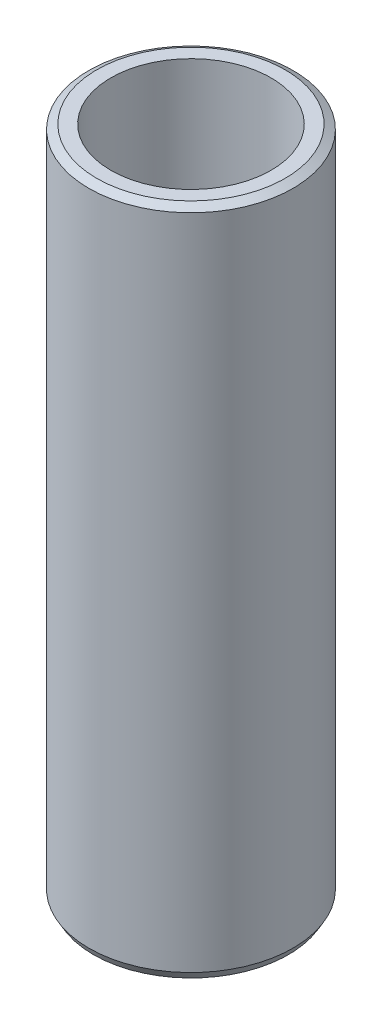
SolidWorks part; units mm, degrees
ref_plane "Front Plane" through (0, 0, 0) normal (0, 0, 1) x (1, 0, 0)
ref_plane "Top Plane" through (0, 0, 0) normal (0, 1, 0) x (1, 0, 0)
ref_plane "Right Plane" through (0, 0, 0) normal (1, 0, 0) x (0, 0, -1)
sketch "Sketch1" plane through (0, 0, 0) normal (0, 1, 0) x (1, 0, 0)
  circle A0 centre (0, 0) radius 30
  dimension "SHAFT_OD" = 60
extrude "Boss-Extrude1" add sketch "Sketch1" along normal blind 196.95
sketch "Sketch2" plane through (0, 0, 0) normal (0, 1, 0) x (1, 0, 0)
  circle A0 centre (0, 0) radius 23.5368
  dimension "BORE_D" = 47.0735
extrude "Cut-Extrude1" cut sketch "Sketch2" along normal through all
chamfer "Chamfer1" distance 1.3542 angle 60 2 edges at (0, 196.95, 30) (0, 0, 30) first distance on face at (0, 196.95, 30) first distance on face at (0, 0, 23.5368)
